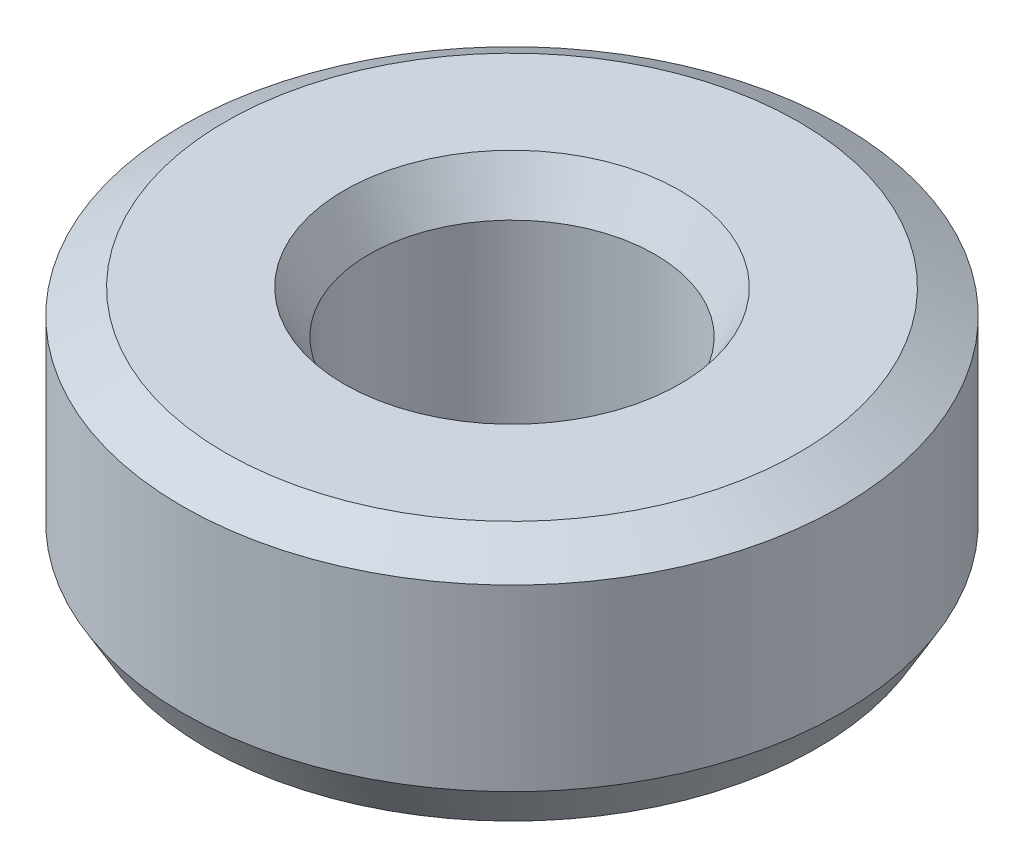
SolidWorks part; units mm, degrees
ref_plane "Front Plane" through (0, 0, 0) normal (0, 0, 1) x (1, 0, 0)
ref_plane "Top Plane" through (0, 0, 0) normal (0, 1, 0) x (1, 0, 0)
ref_plane "Right Plane" through (0, 0, 0) normal (1, 0, 0) x (0, 0, -1)
sketch "Sketch1" plane through (0, 0, 0) normal (0, 1, 0) x (1, 0, 0)
  circle A0 centre (0, 0) radius 37.5
  dimension "SLEEVE_OD" = 75
extrude "Boss-Extrude1" add sketch "Sketch1" along normal blind 28.0668
sketch "Sketch2" plane through (0, 0, 0) normal (0, 1, 0) x (1, 0, 0)
  circle A0 centre (0, 0) radius 16.2654
  dimension "BORE_D" = 32.5309
extrude "Cut-Extrude1" cut sketch "Sketch2" along normal through all
chamfer "Chamfer1" distance 2.823 angle 60 4 edges at (0, 28.0668, 16.2654) (0, 0, 16.2654) (0, 0, 37.5) (0, 28.0668, 37.5) first distance on face at (0, 28.0668, 16.2654) first distance on face at (0, 0, 16.2654) first distance on face at (0, 28.0668, 37.5)
